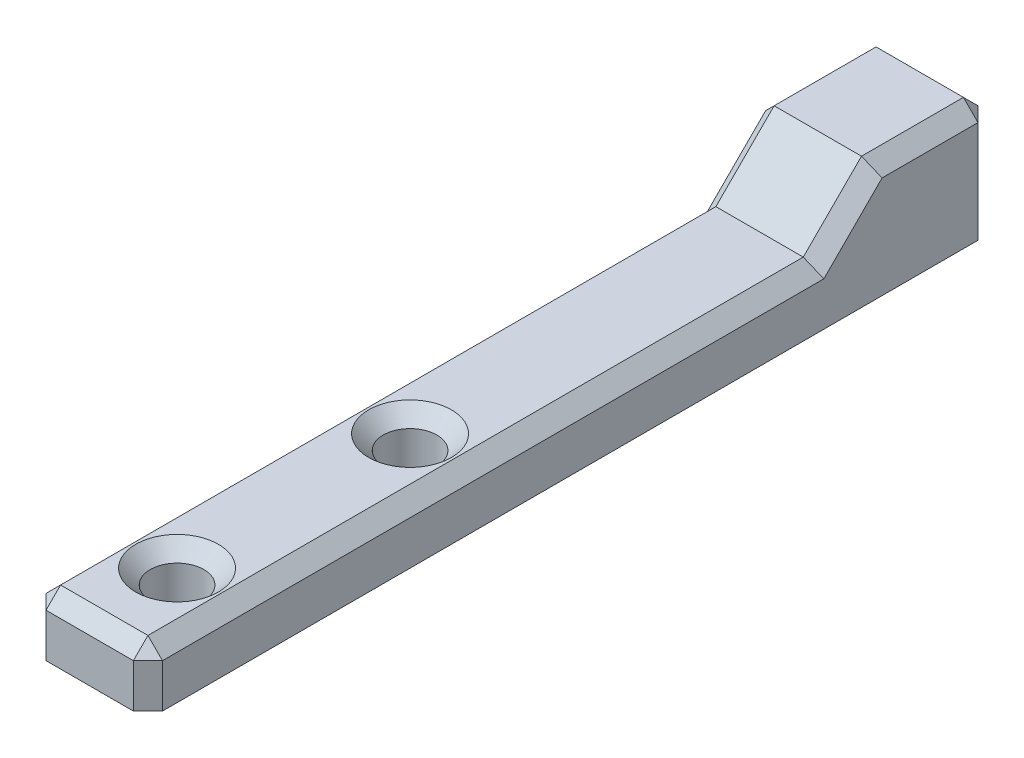
SolidWorks part; units mm, degrees
ref_plane "Front Plane" through (0, 0, 0) normal (0, 0, 1) x (1, 0, 0)
ref_plane "Top Plane" through (0, 0, 0) normal (0, 1, 0) x (1, 0, 0)
ref_plane "Right Plane" through (0, 0, 0) normal (1, 0, 0) x (0, 0, -1)
sketch "Sketch1" plane through (0, 0, 0) normal (0, 1, 0) x (1, 0, 0)
  line L1 (0, 0) -> (12.7, 0)
  line L2 (0, 0) -> (0, 92.075)
  line L3 (0, 92.075) -> (12.7, 92.075)
  line L4 (12.7, 0) -> (12.7, 92.075)
  circle A0 centre (6.35, 9.525) radius 2.921
  circle A1 centre (6.35, 34.925) radius 2.921
  dimension "D3" = 5.842
  dimension "D1" = 12.7
  dimension "0.375" = 9.525
  dimension "D4" = 25.4
  dimension "D5" = 57.15
extrude "Boss-Extrude1" add sketch "Sketch1" along normal blind 12.7
sketch "Sketch2" plane through (12.7, 0, 0) normal (1, 0, 0) x (0, 0, -1)
  line L0 (92.075, 12.7) -> (92.075, 0) construction
  line L1 (0, 12.7) -> (79.375, 12.7)
  line L2 (0, 12.7) -> (0, 6.35)
  line L3 (0, 6.35) -> (79.375, 6.35)
  line L4 (79.375, 12.7) -> (79.375, 6.35)
  dimension "D1" = 12.7
  dimension "D2" = 6.35
extrude "Cut-Extrude1" cut sketch "Sketch2" against normal through all
chamfer "Chamfer1" distance 6.35 angle 45 1 edges at (6.35, 6.35, -79.375)
chamfer "Chamfer2" distance 1.5875 angle 45 14 edges at (0, 3.175, 0) (12.7, 3.175, 0) (0, 6.35, -92.075) (12.7, 6.35, -92.075) (0, 9.525, -76.2) (0, 12.7, -85.725) (6.35, 12.7, -92.075) (12.7, 12.7, -85.725) (12.7, 9.525, -76.2) (0, 6.35, -36.5125) (6.35, 6.35, 0) (12.7, 6.35, -36.5125) (6.35, 6.35, -12.446) (6.35, 6.35, -37.846)
